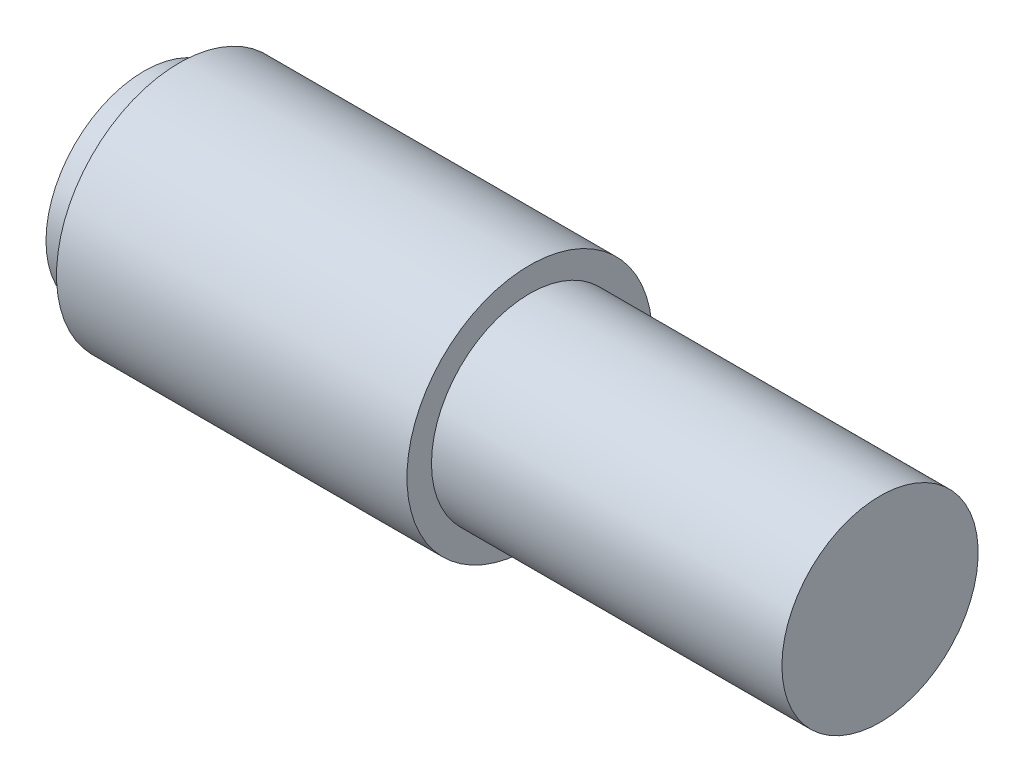
SolidWorks part; units mm, degrees
ref_plane "Front Plane" through (0, 0, 0) normal (0, 0, 1) x (1, 0, 0)
ref_plane "Top Plane" through (0, 0, 0) normal (0, 1, 0) x (1, 0, 0)
ref_plane "Right Plane" through (0, 0, 0) normal (1, 0, 0) x (0, 0, -1)
sketch "Sketch1" plane through (0, 0, 0) normal (1, 0, 0) x (0, 0, -1)
  circle A0 centre (0, 0) radius 1.75
  dimension "D1" = 3.5
extrude "Boss-Extrude1" add sketch "Sketch1" along normal blind 5
sketch "Sketch2" plane through (0, 0, 0) normal (-1, 0, 0) x (0, 0, 1)
  circle A0 centre (0, 0) radius 1.4
  dimension "D1" = 2.8
extrude "Boss-Extrude2" add sketch "Sketch2" against normal blind 10
extrude "Boss-Extrude3" add sketch "Sketch2<2>" along normal blind 0.5
sketch "Sketch2<2>" plane through (0, 0, 0) normal (-1, 0, 0) x (0, 0, 1) same geometry as "Sketch2"
